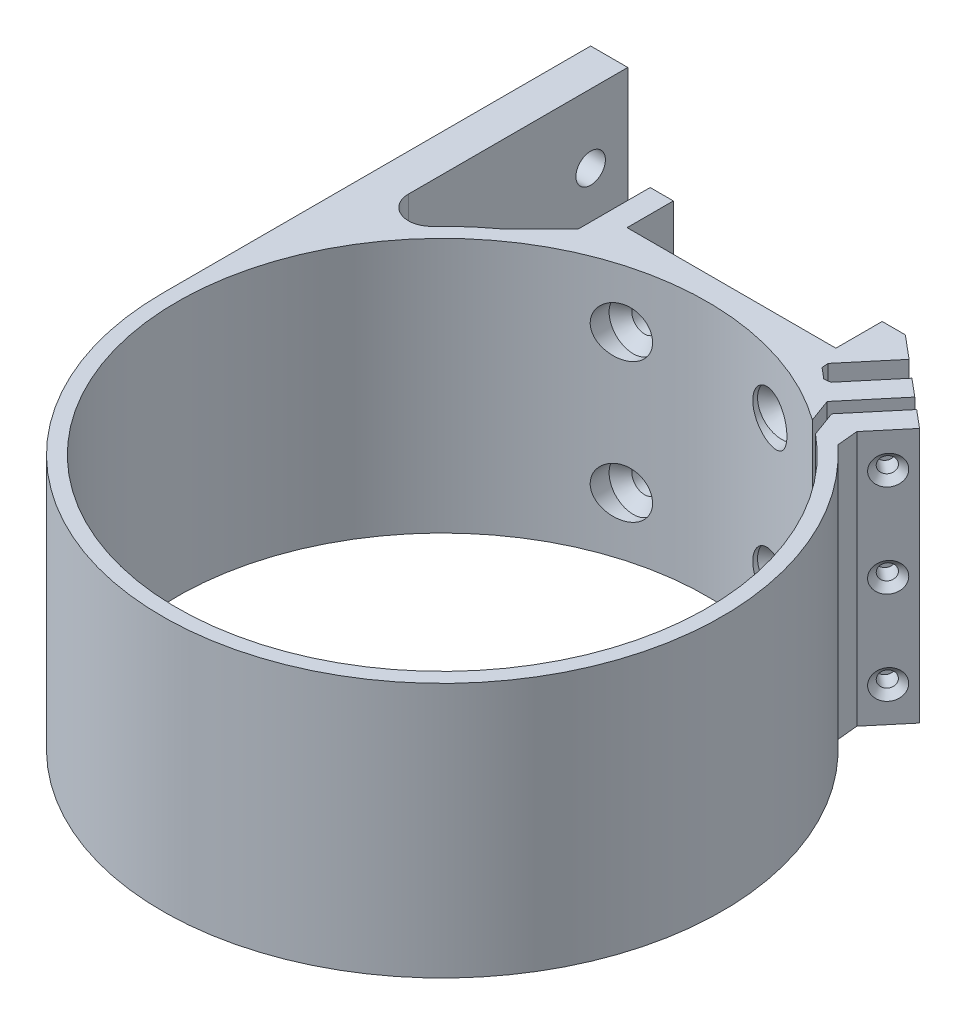
SolidWorks part; units mm, degrees
ref_plane "Front Plane" through (0, 0, 0) normal (0, 0, 1) x (1, 0, 0)
ref_plane "Top Plane" through (0, 0, 0) normal (0, 1, 0) x (1, 0, 0)
ref_plane "Right Plane" through (0, 0, 0) normal (1, 0, 0) x (0, 0, -1)
sketch "Sketch1" plane through (0, 0, 0) normal (0, 1, 0) x (1, 0, 0)
  line L0 (-27.5, 53.6922) -> (-27.5, 72.3012)
  line L5 (-27.5, 72.3012) -> (-22.5, 72.3012)
  line L6 (-22.5, 72.3012) -> (-22.5, 62.325)
  line L7 (-22.5, 62.325) -> (22.5, 62.325)
  line L8 (22.5, 62.325) -> (22.5, 72.3012)
  line L9 (22.5, 72.3012) -> (27.5, 72.3012)
  line L10 (27.5, 72.3012) -> (27.5, 53.6922) construction
  line L11 (31.5122, 51.4401) -> (33.3405, 46.4169)
  line L12 (34.3018, 49.6235) -> (36.2961, 44.1443)
  line L14 (31.5122, 51.4401) -> (40.1266, 61.7062)
  line L15 (34.3018, 49.6235) -> (42.658, 59.5821)
  line L16 (42.658, 59.5821) -> (46.4882, 56.3682)
  line L17 (46.4882, 56.3682) -> (38.2986, 46.6082)
  line L18 (40.1266, 61.7062) -> (36.2963, 64.9202)
  line L19 (36.2963, 64.9202) -> (27.682, 54.654)
  line L20 (27.682, 54.654) -> (23.8518, 57.868)
  line L21 (23.8518, 57.868) -> (32.4661, 68.1341)
  line L22 (32.4661, 68.1341) -> (27.5, 72.3012)
  line L23 (-60.325, 0) -> (-60.325, 92.3012)
  line L24 (-60.325, 92.3012) -> (-52.325, 92.3012)
  line L25 (-52.325, 92.3012) -> (-52.325, 30.02)
  arc A0 (-27.5, 53.6922) -> (-52.325, 30.02) centre (0, 0) ccw
  arc A1 (33.3405, 46.4169) -> (36.2961, 44.1443) centre (0, 0) ccw
  arc A2 (31.5122, 51.4401) -> (27.5, 53.6922) centre (0, 0) ccw construction
  arc A3 (38.2986, 46.6082) -> (34.3018, 49.6235) centre (0, 0) ccw construction
  arc A4 (-60.325, 0) -> (38.2986, 46.6082) centre (0, 0) ccw
  point P9 (0, 62.325)
  point P13 (0, 60.325)
  dimension "D1" = 114.3
  dimension "D2" = 3.175
  dimension "D3" = 45
  dimension "D4" = 5
  dimension "D5" = 5
  dimension "D6" = 2
  dimension "D7" = 20
  dimension "D8" = 2
  dimension "D9" = 3
  dimension "D10" = 120
  dimension "D11" = 13
  dimension "D12" = 5
  dimension "D13" = 5
  dimension "D14" = 8
  dimension "D15" = 20
extrude "Boss-Extrude1" add sketch "Sketch1" along normal mid plane 55
sketch "Sketch4" plane through (0, -27.5, 0) normal (0, -1, 0) x (1, 0, 0)
  line L1 (-22.5, -62.325) -> (22.5, -62.325)
  line L2 (-22.5, -62.325) -> (-22.5, -72.3012)
  line L3 (-22.5, -72.3012) -> (22.5, -72.3012)
  line L4 (22.5, -62.325) -> (22.5, -72.3012)
extrude "Boss-Extrude2" add sketch "Sketch4" against normal blind 4.5
ref_plane "Plane1" through (0, 0, -57.15) normal (0, 0, 1) x (1, 0, 0)
sketch "Sketch6" plane through (0, 0, -57.15) normal (0, 0, 1) x (1, 0, 0)
  line L1 (16, -15) -> (-16, -15) construction
  line L2 (16, -15) -> (16, 15) construction
  line L3 (16, 15) -> (-16, 15) construction
  line L4 (-16, -15) -> (-16, 15) construction
  line L5 (16, -15) -> (-16, 15) construction
  line L6 (16, 15) -> (-16, -15) construction
  point P0 (0, 0)
  dimension "D1" = 32
  dimension "D2" = 30
hole_wizard "CSK for M5 Flat Head Machine Screw1" positions "Sketch10" profile "Sketch12" countersink size "M5" standard "ANSI Metric" end condition through all
sketch "Sketch10" plane through (0, 0, -57.15) normal (0, 0, 1) x (1, 0, 0)
  point P0 (-16, 15)
  point P3 (16, 15)
  point P6 (16, -15)
  point P9 (-16, -15)
sketch "Sketch12" plane through (-16, 15, -57.15) normal (1, 0, 0) x (0, -1, 0)
  line L0 (0, 0) -> (0, 35.1512)
  line L1 (0, 35.1512) -> (2.75, 35.1512)
  line L2 (2.75, 35.1512) -> (2.75, 2.45)
  line L3 (2.75, 2.45) -> (5.2, 0)
  line L5 (5.2, 0) -> (0, 0)
  line L6 (-2.75, 2.45) -> (-5.2, 0) construction
  line L11 (0, -6.35) -> (0, 107.95) construction
  dimension "Thru Hole Dia." = 5.5
  dimension "Thru Hole Depth" = 35.1512
  dimension "Near C'Sink Dia." = 10.4
  dimension "Near C'Sink Angle" = 90
sketch "Sketch13" plane through (0, 0, -57.15) normal (0, 0, 1) x (1, 0, 0)
  circle A0 centre (-16, -15) radius 5.2 construction
  circle A1 centre (16, -15) radius 5.2 construction
  circle A2 centre (16, 15) radius 5.2 construction
  circle A3 centre (-16, 15) radius 5.2 construction
  circle A4 centre (-16, -15) radius 5.2
  circle A5 centre (16, -15) radius 5.2
  circle A6 centre (16, 15) radius 5.2
  circle A7 centre (-16, 15) radius 5.2
extrude "Cut-Extrude1" cut sketch "Sketch13" along normal up to next
chamfer "Chamfer1" distance 3.175 angle 45 2 edges at (-27.5, 0, -53.6922) (38.2986, 0, -46.6082) first distance on face at (-27.5, 0, -62.9967) first distance on face at (7.3811, 0, 15.6185)
chamfer "Chamfer2" distance 1 angle 45 2 edges at (23.8518, 0, -57.868) (27.682, 0, -54.654)
hole_wizard "CSK for M3 Flat Head Machine Screw1" positions "Sketch2" profile "Sketch3" countersink size "M3" standard "ANSI Metric"
sketch "Sketch2" plane through (-0.4755, 0, -0.399) normal (0.766, 0, 0.6428) x (0.6428, 0, -0.766)
  line L0 (63.4646, 27.5) -> (73.0626, 27.5) construction
  point P0 (68.2636, 20)
  point P2 (68.2636, 0)
  point P4 (68.2636, -20)
  point P16 (68.2636, 27.5)
  point P17 (0, 0)
  point P18 (60.3218, 27.5)
  point P22 (0, 0)
  point P23 (63.4646, 27.5)
  point P25 (63.4646, 27.5)
  dimension "D1" = 20
  dimension "D2" = 20
sketch "Sketch3" plane through (43.4035, 20, -52.6919) normal (0, 1, 0) x (0.6428, 0, -0.766)
  line L0 (0, 0) -> (0, 16.0215)
  line L1 (0, 16.0215) -> (1.7, 15)
  line L2 (1.7, 15) -> (1.7, 1.45)
  line L3 (1.7, 1.45) -> (3.15, 0)
  line L5 (3.15, 0) -> (0, 0)
  line L6 (-1.7, 1.45) -> (-3.15, 0) construction
  line L10 (0, 16.0215) -> (-1.7, 15) construction
  line L11 (0, -6.35) -> (0, 107.95) construction
  dimension "Hole Dia." = 3.4
  dimension "Hole Depth" = 15
  dimension "Near C'Sink Dia." = 6.3
  dimension "Near C'Sink Angle" = 90
  dimension "Drill Angle" = 118
fillet "Fillet2" radius 5 1 edges at (-52.325, 0, -30.02)
sketch "Sketch14" plane through (-52.325, 0, 0) normal (1, 0, 0) x (0, 0, -1)
  line L0 (84.3012, 12.7) -> (84.3012, -12.7) construction
  line L1 (84.3012, 12.7) -> (84.3012, 27.5) construction
  line L2 (84.3012, -12.7) -> (84.3012, -27.5) construction
  line L3 (45.03, -27.5) -> (92.3012, -27.5) construction
  line L4 (45.03, 27.5) -> (92.3012, 27.5) construction
  line L5 (92.3012, 27.5) -> (92.3012, -27.5) construction
  arc A0 (84.3012, 38.1) -> (84.3012, -38.1) centre (84.3012, 0) ccw construction
  circle A1 centre (84.3012, 12.7) radius 3.175
  circle A2 centre (84.3012, -12.7) radius 3.175
  dimension "D1" = 38.1
  dimension "D4" = 6.35
  dimension "D2" = 25.4
  dimension "D3" = 8
extrude "Cut-Extrude2" cut sketch "Sketch14" against normal blind 10
